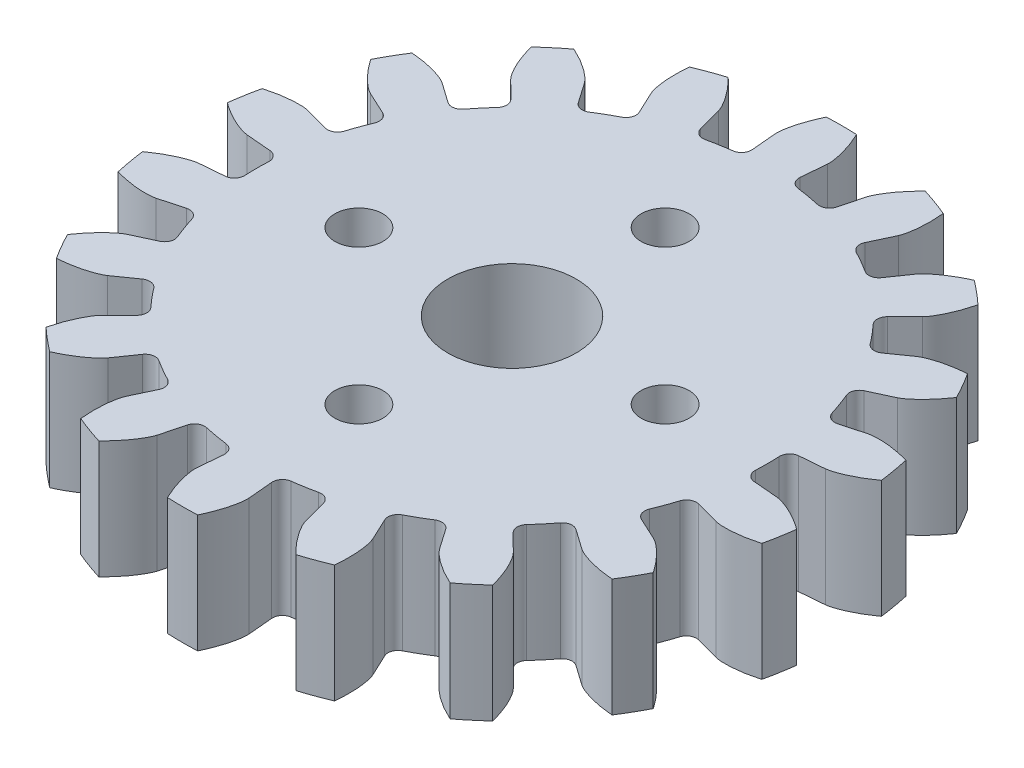
SolidWorks part; units mm, degrees
material "PMMA"
ref_plane "Plan de face" through (0, 0, 0) normal (0, 0, 1) x (1, 0, 0)
ref_plane "Plan de dessus" through (0, 0, 0) normal (0, 1, 0) x (1, 0, 0)
ref_plane "Plan de droite" through (0, 0, 0) normal (1, 0, 0) x (0, 0, -1)
sketch "Esquisse1" plane through (0, 0, 0) normal (0, 1, 0) x (1, 0, 0)
  circle A0 centre (0, 0) radius 14
  dimension "D1" = 28.0001
extrude "Boss.-Extru.1" add sketch "Esquisse1" along normal blind 5
sketch "Esquisse2" plane through (0, 5, 0) normal (0, 1, 0) x (1, 0, 0)
  line L0 (0, 0) -> (12.2811, 1.0359) construction
  line L1 (0, 0) -> (12.2811, -1.0359) construction
  line L2 (12.2811, 1.0359) -> (10.8116, 0.9119)
  line L3 (12.2811, -1.0359) -> (10.8116, -0.9119)
  circle A0 centre (0, 0) radius 14 construction
  circle A1 centre (0, 0) radius 12.6 construction
  circle A2 centre (0, 0) radius 12.3247 construction
  circle A3 centre (0, 0) radius 10.85 construction
  arc A4 (13.8842, 1.7976) -> (13.8842, -1.7976) centre (0, 0) cw
  arc A5 (12.2811, 1.0359) -> (12.2811, -1.0359) centre (0, 0) cw construction
  arc A6 (10.8116, 0.9119) -> (10.8116, -0.9119) centre (0, 0) cw
  spline S0 degree 4 poles (12.2811, 1.0359) (12.2837, 1.0361) (12.2911, 1.0369) (12.305, 1.0388) (12.3277, 1.0424) (12.3564, 1.0478) (12.3935, 1.0555) (12.4371, 1.0658) (12.4848, 1.0783) (12.5365, 1.0932) (12.588, 1.1092) (12.6391, 1.1261) (12.6899, 1.144) (12.7512, 1.1667) (12.8245, 1.1955) (12.9097, 1.2314) (13.0058, 1.2748) (13.1033, 1.3218) (13.1986, 1.3704) (13.2944, 1.4222) (13.3866, 1.4742) (13.4818, 1.5309) (13.5693, 1.5846) (13.6667, 1.6478) (13.745, 1.6996) (13.8475, 1.7712) (13.9078, 1.8144) (13.9781, 1.8661) (14.0092, 1.8896) (14.0283, 1.9041) knots 0 0 0 0 0 0.005377 0.015084 0.028532 0.04661 0.064855 0.092111 0.119476 0.146842 0.174209 0.201575 0.228941 0.256307 0.307035 0.361767 0.4165 0.471232 0.525964 0.580697 0.635429 0.690161 0.744894 0.799626 0.854358 0.909091 0.954545 1 1 1 1 1 construction
  spline S1 degree 4 poles (12.2811, 1.0359) (12.2837, 1.0361) (12.2911, 1.0369) (12.305, 1.0388) (12.3277, 1.0424) (12.3564, 1.0478) (12.3935, 1.0555) (12.4371, 1.0658) (12.4848, 1.0783) (12.5365, 1.0932) (12.588, 1.1092) (12.6391, 1.1261) (12.6899, 1.144) (12.7512, 1.1667) (12.8245, 1.1955) (12.9097, 1.2314) (13.0058, 1.2748) (13.1033, 1.3218) (13.1986, 1.3704) (13.2944, 1.4222) (13.3866, 1.4742) (13.4818, 1.5309) (13.5693, 1.5846) (13.6667, 1.6478) (13.745, 1.6996) (13.8253, 1.7557) (13.8643, 1.7833) (13.8842, 1.7976) knots 0 0 0 0 0 0.005377 0.015084 0.028532 0.04661 0.064855 0.092111 0.119476 0.146842 0.174209 0.201575 0.228941 0.256307 0.307035 0.361767 0.4165 0.471232 0.525964 0.580697 0.635429 0.690161 0.744894 0.799626 0.854358 0.909091 0.909091 0.909091 0.909091 0.909091
  spline S2 degree 4 poles (12.2811, -1.0359) (12.2837, -1.0361) (12.2911, -1.0369) (12.305, -1.0388) (12.3277, -1.0424) (12.3564, -1.0478) (12.3935, -1.0555) (12.4371, -1.0658) (12.4848, -1.0783) (12.5365, -1.0932) (12.588, -1.1092) (12.6391, -1.1261) (12.6899, -1.144) (12.7512, -1.1667) (12.8245, -1.1955) (12.9097, -1.2314) (13.0058, -1.2748) (13.1033, -1.3218) (13.1986, -1.3704) (13.2944, -1.4222) (13.3866, -1.4742) (13.4818, -1.5309) (13.5693, -1.5846) (13.6667, -1.6478) (13.745, -1.6996) (13.8475, -1.7712) (13.9078, -1.8144) (13.9781, -1.8661) (14.0092, -1.8896) (14.0283, -1.9041) knots 0 0 0 0 0 0.005377 0.015084 0.028532 0.04661 0.064855 0.092111 0.119476 0.146842 0.174209 0.201575 0.228941 0.256307 0.307035 0.361767 0.4165 0.471232 0.525964 0.580697 0.635429 0.690161 0.744894 0.799626 0.854358 0.909091 0.954545 1 1 1 1 1 construction
  spline S3 degree 4 poles (12.2811, -1.0359) (12.2837, -1.0361) (12.2911, -1.0369) (12.305, -1.0388) (12.3277, -1.0424) (12.3564, -1.0478) (12.3935, -1.0555) (12.4371, -1.0658) (12.4848, -1.0783) (12.5365, -1.0932) (12.588, -1.1092) (12.6391, -1.1261) (12.6899, -1.144) (12.7512, -1.1667) (12.8245, -1.1955) (12.9097, -1.2314) (13.0058, -1.2748) (13.1033, -1.3218) (13.1986, -1.3704) (13.2944, -1.4222) (13.3866, -1.4742) (13.4818, -1.5309) (13.5693, -1.5846) (13.6667, -1.6478) (13.745, -1.6996) (13.8253, -1.7557) (13.8643, -1.7833) (13.8842, -1.7976) knots 0 0 0 0 0 0.005377 0.015084 0.028532 0.04661 0.064855 0.092111 0.119476 0.146842 0.174209 0.201575 0.228941 0.256307 0.307035 0.361767 0.4165 0.471232 0.525964 0.580697 0.635429 0.690161 0.744894 0.799626 0.854358 0.909091 0.909091 0.909091 0.909091 0.909091
  dimension "D1" = 28.0001
  dimension "D2" = 25.2001
  dimension "D3" = 24.6494
  dimension "D4" = 21.7001
extrude "Enlèv. mat.-Extru.3" cut sketch "Esquisse2" against normal through all
fillet "Congé1" radius 0.4228 2 edges at (10.8116, 2.5, 0.9119) (10.8116, 2.5, -0.9119)
pattern_circular "Répétition circulaire2" count 18 over 360 about axis through (0, 5, 0) along (0, -1, 0) of "Enlèv. mat.-Extru.3", "Congé1" reverse direction yes
sketch "Esquisse3" plane through (0, 5, 0) normal (0, 1, 0) x (1, 0, 0)
  circle A0 centre (0, 0) radius 2.725
  dimension "D1" = 5.45
extrude "Enlèv. mat.-Extru.4" cut sketch "Esquisse3" against normal through all
sketch "Esquisse4" plane through (0, 5, 0) normal (0, 1, 0) x (1, 0, 0)
  line L0 (0, 0) -> (6.5, 0) construction
  circle A0 centre (6.5, 0) radius 1.02
  dimension "D1" = 2.04
  dimension "D2" = 6.5
extrude "Enlèv. mat.-Extru.5" cut sketch "Esquisse4" against normal through all
pattern_circular "Répétition circulaire3" count 4 over 360 about axis through (0, 0, 0) along (0, 1, 0) of "Enlèv. mat.-Extru.5"
equation "\"DiametralPitch\"= 18.1428/25.4"
equation "\"NumTeeth\"= 18"
equation "\"PressureAngle\"= 12"
equation "\"Addendum\"= 1 / \"DiametralPitch\""
equation "\"Dedendum\"= 1.25 / \"DiametralPitch\""
equation "\"WorkingDepth\"= 2 / \"DiametralPitch\""
equation "\"WholeDepth\"= 2.25 / \"DiametralPitch\""
equation "\"Clearance\"= 0.25 / \"DiametralPitch\""
equation "\"ToothThickness\"= 1.5708 / \"DiametralPitch\""
equation "\"CircularPitch\"= pi / \"DiametralPitch\""
equation "\"PitchCircle\"= \"NumTeeth\" / \"DiametralPitch\""
equation "\"OutsideDiameter\"= ( \"NumTeeth\" + 2 ) / \"DiametralPitch\""
equation "\"Fillet\"= \"Clearance\" * cos ( \"PressureAngle\" ) * tan ( ( 90 + \"PressureAngle\" ) / 2 )"
equation "\"AddendumCircle\"= \"PitchCircle\" + ( 2 * \"Addendum\" )"
equation "\"DedendumCircle\"= \"PitchCircle\" - ( 2 * \"Dedendum\" )"
equation "\"BaseCircle\"= \"PitchCircle\" * cos ( \"PressureAngle\" )"
equation "\"PitchAngle\"= 360deg / \"NumTeeth\""
equation "\"Alpha\"= sqr ( \"PitchCircle\" ^ 2 - \"BaseCircle\" ^ 2 ) / \"BaseCircle\" * 180 / PI - \"PressureAngle\""
equation "\"Beta\"= ( \"PitchAngle\" / 4 - \"Alpha\" )"
equation "\"Phi\"= sqr ( ( \"AddendumCircle\" / 2 ) ^ 2 - ( \"BaseCircle\" / 2 ) ^ 2 ) / ( \"BaseCircle\" / 2 )"
equation "\"D1@Esquisse1\"=\"OutsideDiameter\""
equation "\"D1@Esquisse2\"=\"OutsideDiameter\""
equation "\"D2@Esquisse2\"=\"PitchCircle\""
equation "\"D3@Esquisse2\"=\"BaseCircle\""
equation "\"D4@Esquisse2\"=\"DedendumCircle\""
equation "\"D1@Congé1\"=\"Fillet\""
equation "\"D1@Répétition circulaire2\"=\"NumTeeth\""
